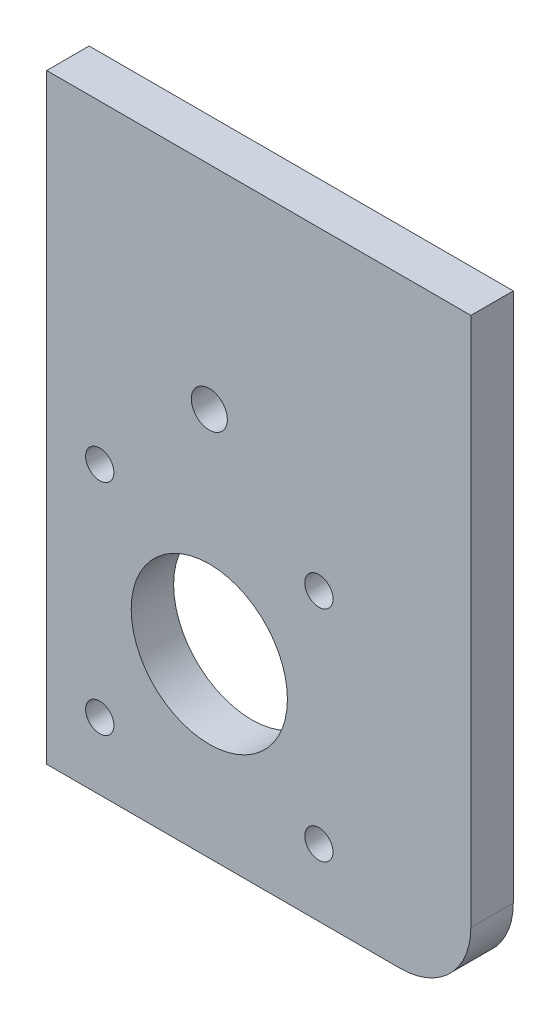
SolidWorks part; units mm, degrees
material "Клен"
ref_plane "Спереди" through (0, 0, 0) normal (0, 0, 1) x (1, 0, 0)
ref_plane "Сверху" through (0, 0, 0) normal (0, 1, 0) x (1, 0, 0)
ref_plane "Справа" through (0, 0, 0) normal (1, 0, 0) x (0, 0, -1)
sketch "Эскиз1" plane through (0, 0, 0) normal (0, 0, 1) x (1, 0, 0)
  line L0 (6, -293.8462) -> (6, -378.8462)
  line L1 (6, -293.8462) -> (6, -593.8462) construction
  line L7 (6, -293.8462) -> (66, -293.8462)
  line L11 (66, -293.8462) -> (66, -287.8462) construction
  line L12 (66, -293.8462) -> (66, -368.8462)
  line L14 (56, -378.8462) -> (6, -378.8462)
  arc A0 (66, -368.8462) -> (56, -378.8462) centre (56, -368.8462) cw
  circle A1 centre (29, -323.8462) radius 2.55
  dimension "D3" = 5.1
  dimension "D2" = 10
  dimension "D1" = 85
extrude "Бобышка-Вытянуть1" add sketch "Эскиз1" against normal blind 6 contours L0 L14 A0 L12 L7
sketch "Эскиз2" plane through (0, 0, 0) normal (0, 0, 1) x (1, 0, 0)
  line L0 (6, -293.8462) -> (6, -378.8462) construction
  line L2 (29, -353.8462) -> (29, -402.3555) construction
  line L3 (29, -353.8462) -> (54.8419, -353.8462) construction
  line L5 (6, -293.8462) -> (66, -293.8462) construction
  circle A0 centre (29, -353.8462) radius 11.05
  circle A1 centre (44.5, -369.3462) radius 2
  circle A2 centre (13.5, -369.3462) radius 2
  circle A3 centre (13.5, -338.3462) radius 2
  circle A4 centre (44.5, -338.3462) radius 2
  circle A5 centre (29, -323.8462) radius 2.55
  dimension "D2" = 22.1
  dimension "D3" = 4
  dimension "D6" = 5.1
  dimension "D1" = 60
  dimension "D4" = 15.5
  dimension "D5" = 15.5
  dimension "D7" = 23
extrude "Вырез-Вытянуть1" cut sketch "Эскиз2" against normal through all
